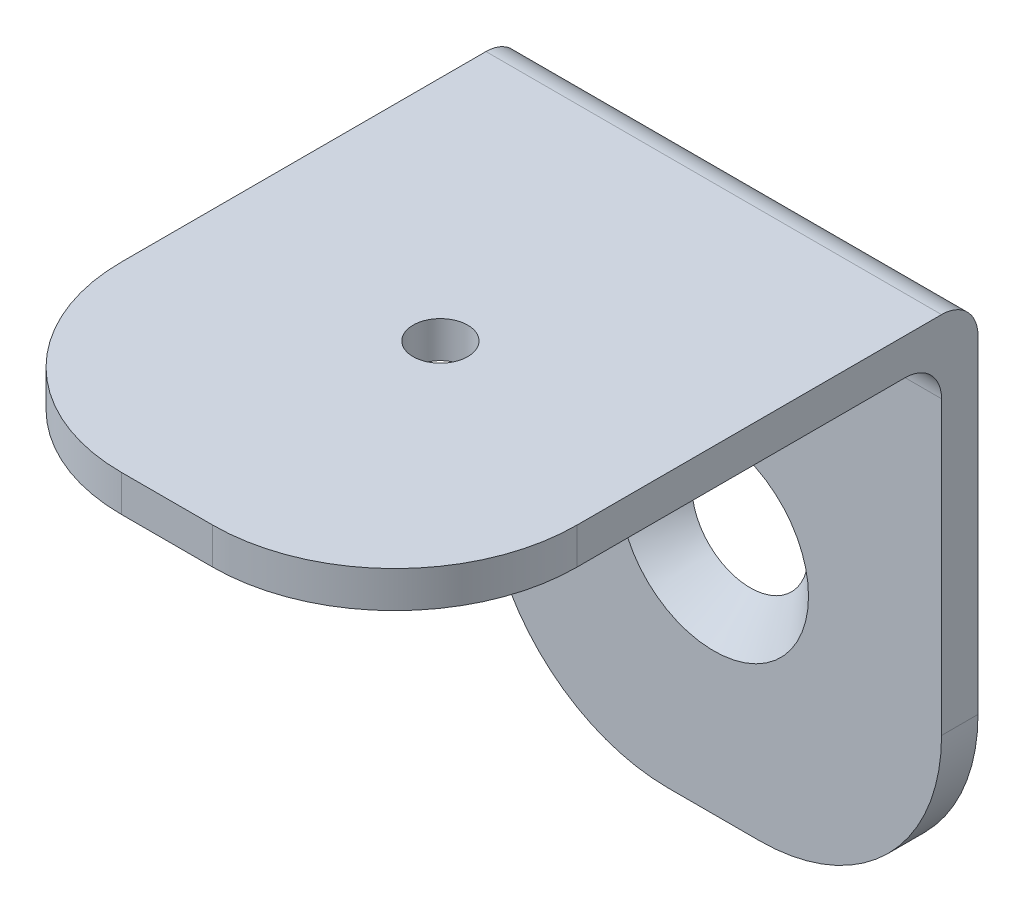
SolidWorks part; units mm, degrees
ref_plane "Спереди" through (0, 0, 0) normal (0, 0, 1) x (1, 0, 0)
ref_plane "Сверху" through (0, 0, 0) normal (0, 1, 0) x (1, 0, 0)
ref_plane "Справа" through (0, 0, 0) normal (1, 0, 0) x (0, 0, -1)
sketch "Эскиз1" plane through (0, 0, 0) normal (0, 1, 0) x (1, 0, 0)
  line L1 (-2.5, -15) -> (2.5, -15)
  line L2 (-12.5, -5) -> (-12.5, 15)
  line L3 (-12.5, 15) -> (12.5, 15)
  line L4 (12.5, -5) -> (12.5, 15)
  line L5 (-12.5, -15) -> (12.5, 15) construction
  line L6 (-12.5, 15) -> (12.5, -15) construction
  arc A0 (2.5, -15) -> (12.5, -5) centre (2.5, -5) ccw
  arc A1 (-2.5, -15) -> (-12.5, -5) centre (-2.5, -5) cw
  point P0 (0, 0)
  dimension "D3" = 10
  dimension "D1" = 25
  dimension "D2" = 30
  dimension "D4" = 15
extrude "Бобышка-Вытянуть1" add sketch "Эскиз1" along normal blind 2
sketch "Эскиз3" plane through (0, 0, -15) normal (0, 0, -1) x (-1, 0, 0)
  line L0 (-2.5, -28) -> (2.5, -28)
  line L1 (-12.5, -18) -> (-12.5, 2)
  line L2 (-12.5, 2) -> (12.5, 2)
  line L3 (12.5, -18) -> (12.5, 2)
  line L4 (-12.5, 0) -> (12.5, 0) construction
  arc A0 (2.5, -28) -> (12.5, -18) centre (2.5, -18) ccw
  arc A1 (-2.5, -28) -> (-12.5, -18) centre (-2.5, -18) cw
  dimension "D1" = 28
  dimension "D2" = 25
extrude "Бобышка-Вытянуть2" add sketch "Эскиз3" along normal blind 2
fillet "Скругление1" radius 2 1 edges at (0, 0, -15)
fillet "Скругление2" radius 2 1 edges at (0, 2, -17)
hole_wizard "Зенковка для винта с полупотайной головкой M52" positions "Эскиз6" profile "Эскиз7" countersink size "M5" standard "ISO" end condition through all
sketch "Эскиз6" plane through (0, 0, -15) normal (0, 0, 1) x (1, 0, 0)
  point P0 (0, -15.0342)
sketch "Эскиз7" plane through (0, -15.0342, -15) normal (1, 0, 0) x (0, -1, 0)
  line L0 (0, 0) -> (0, 2)
  line L1 (0, 2) -> (2.75, 2)
  line L2 (2.75, 2) -> (2.75, 2.45)
  line L3 (2.75, 2.45) -> (5.2, 0)
  line L5 (5.2, 0) -> (0, 0)
  line L6 (-2.75, 2.45) -> (-5.2, 0) construction
  line L11 (0, -6.35) -> (0, 107.95) construction
  dimension "Диаметр сквозного отверстия" = 5.5
  dimension "Глубина сквозного отверстия" = 2
  dimension "Диаметр передней зенковки" = 10.4
  dimension "Угол передней зенковки" = 90
sketch "Эскиз8" plane through (0, 0, 0) normal (0, -1, 0) x (1, 0, 0)
  circle A0 centre (0, 0) radius 1.5
  dimension "D1" = 3
extrude "Вырез-Вытянуть1" cut sketch "Эскиз8" against normal blind 10
